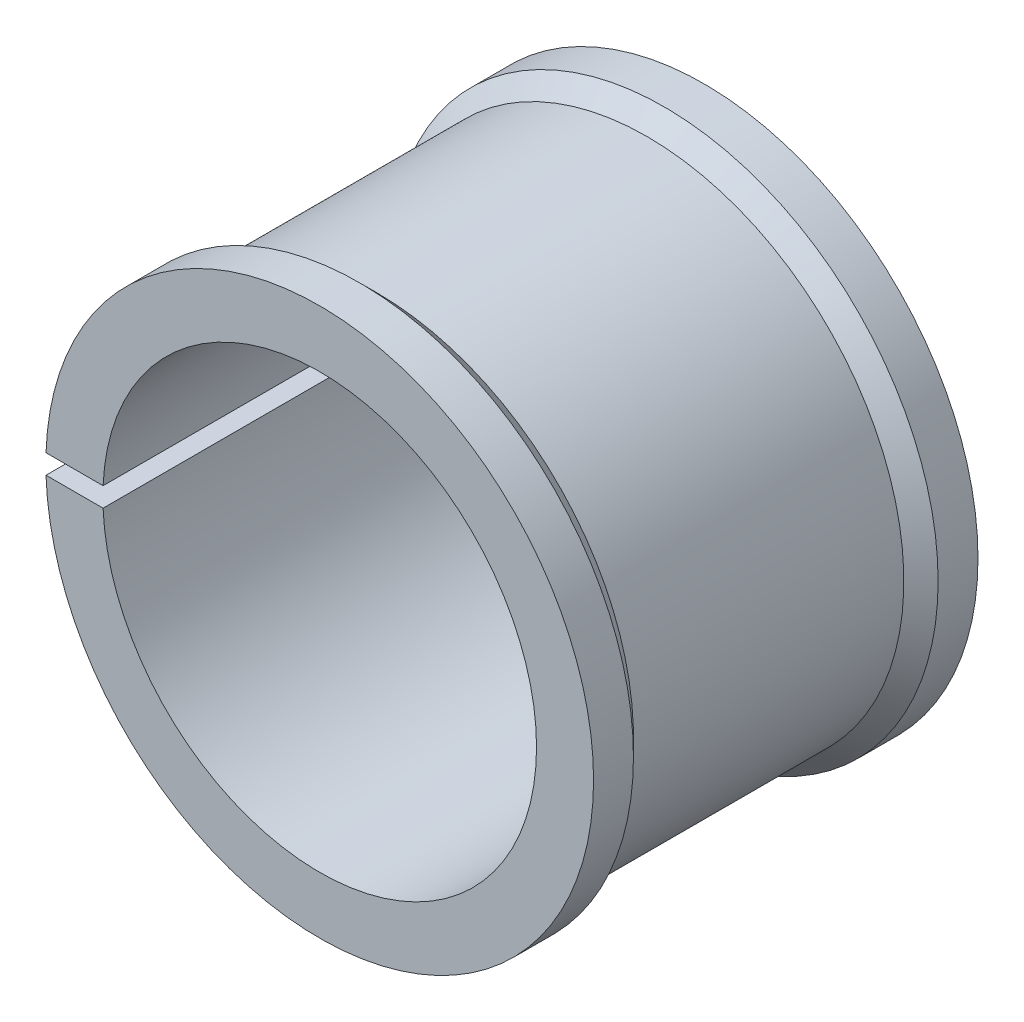
SolidWorks part; units mm, degrees
material "EPİKLORHİDRİN"
ref_plane "Ön Düzlem" through (0, 0, 0) normal (0, 0, 1) x (1, 0, 0)
ref_plane "Üst Düzlem" through (0, 0, 0) normal (0, 1, 0) x (1, 0, 0)
ref_plane "Sağ Düzlem" through (0, 0, 0) normal (1, 0, 0) x (0, 0, -1)
sketch "Çizim1" plane through (0, 0, 0) normal (0, 0, 1) x (1, 0, 0)
  circle A0 centre (0, 0) radius 25.75
extrude "Yükseklik-Ekstrüzyon2" add sketch "Çizim1" along normal blind 22.56
sketch "Çizim2" plane through (0, 0, 22.56) normal (0, 0, 1) x (1, 0, 0)
  circle A0 centre (0, 0) radius 21.75
extrude "Kes-Ekstrüzyon1" cut sketch "Çizim2" against normal blind 22.56
sketch "Çizim3" plane through (0, 0, 22.56) normal (0, 0, 1) x (1, 0, 0)
  circle A0 centre (0, 0) radius 27.47
extrude "Yükseklik-Ekstrüzyon3" add sketch "Çizim3" along normal blind 8
chamfer "Pah1" distance 4 angle 45 1 edges at (27.47, 0, 22.56)
sketch "Çizim5" plane through (0, 0, 0) normal (0, 0, -1) x (-1, 0, 0)
  circle A0 centre (0, 0) radius 27.47
extrude "Yükseklik-Ekstrüzyon4" add sketch "Çizim5" along normal blind 8
chamfer "Pah2" distance 4 angle 45 1 edges at (-27.47, 0, 0)
sketch "Çizim6" plane through (0, 0, 30.56) normal (0, 0, 1) x (1, 0, 0)
  circle A0 centre (0, 0) radius 21.75
extrude "Kes-Ekstrüzyon4" cut sketch "Çizim6" against normal blind 8
sketch "Çizim7" plane through (0, 0, -8) normal (0, 0, -1) x (-1, 0, 0)
  circle A0 centre (0, 0) radius 21.75
extrude "Kes-Ekstrüzyon5" cut sketch "Çizim7" against normal blind 8
sketch "Çizim8" plane through (0, 0, -8) normal (0, 0, -1) x (-1, 0, 0)
  line L1 (21.7281, 0.975) -> (27.4527, 0.975)
  line L2 (21.7281, -0.975) -> (27.4527, -0.975)
  arc A0 (21.7281, -0.975) -> (21.7281, 0.975) centre (0, 0) ccw
  arc A1 (27.4527, -0.975) -> (27.4527, 0.975) centre (0, 0) ccw
extrude "Kes-Ekstrüzyon6" cut sketch "Çizim8" against normal blind 64
